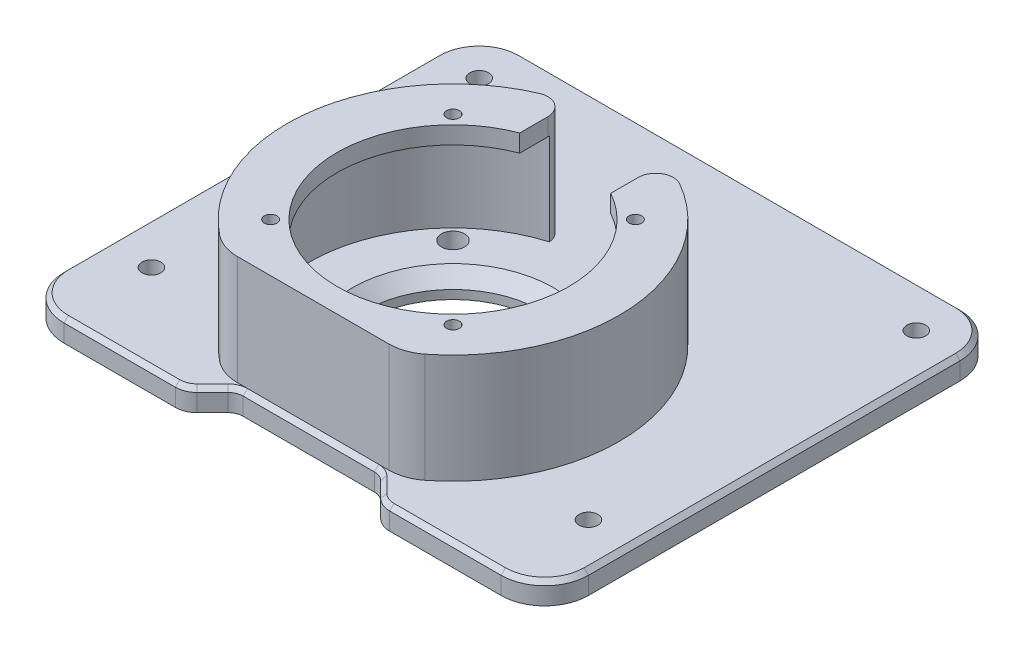
SolidWorks part; units mm, degrees
ref_plane "Front Plane" through (0, 0, 0) normal (0, 0, 1) x (1, 0, 0)
ref_plane "Top Plane" through (0, 0, 0) normal (0, 1, 0) x (1, 0, 0)
ref_plane "Right Plane" through (0, 0, 0) normal (1, 0, 0) x (0, 0, -1)
sketch "Sketch1" plane through (0, 0, 0) normal (0, 1, 0) x (1, 0, 0)
  line L0 (0, 0) -> (0, -28) construction
  line L1 (0, -28) -> (-28, -28) construction
  line L2 (0, -28) -> (28, -28) construction
  line L3 (0, 0) -> (0, 42) construction
  line L4 (0, 42) -> (20, 42) construction
  line L5 (0, 42) -> (-20, 42) construction
  line L6 (-15, -36.5) -> (15, -36.5) construction
  line L7 (-15, -34.85) -> (15, -34.85)
  line L8 (-15, -38.15) -> (15, -38.15)
  line L9 (0, 0) -> (0, -36.5) construction
  circle A0 centre (0, 0) radius 35 construction
  circle A1 centre (28, -28) radius 1.4
  circle A2 centre (-28, -28) radius 1.4
  circle A3 centre (-20, 42) radius 1.4
  circle A4 centre (20, 42) radius 1.4
  arc A5 (-15, -34.85) -> (-15, -38.15) centre (-15, -36.5) ccw
  arc A6 (15, -38.15) -> (15, -34.85) centre (15, -36.5) ccw
  point P15 (0, -36.5)
  dimension "D1" = 70
  dimension "D6" = 2.8
  dimension "D9" = 1.65
  dimension "D2" = 28
  dimension "D3" = 42
  dimension "D4" = 56
  dimension "D5" = 40
  dimension "D7" = 30
  dimension "D8" = 36.5
sketch "Sketch2" plane through (0, 0, 0) normal (0, 1, 0) x (1, 0, 0)
  line L0 (0, 0) -> (0, 66) construction
  line L1 (-60, 66) -> (60, 66)
  line L2 (-60, 66) -> (-60, -39)
  line L4 (60, 66) -> (60, -39)
  line L6 (-60, -39) -> (60, -39)
  dimension "D1" = 120
  dimension "D2" = 105
  dimension "D3" = 66
extrude "Boss-Extrude2" add sketch "Sketch2" along normal blind 5
sketch "Sketch9" plane through (0, 5, 0) normal (0, 1, 0) x (1, 0, 0)
  line L0 (-15, -36.5) -> (15, -36.5) construction
  line L1 (-15, -33) -> (15, -33) construction
  line L2 (-15, -40) -> (15, -40) construction
  line L3 (-17.4749, -34.0251) -> (-23.4497, -40)
  line L4 (-23.4497, -40) -> (23.4497, -40)
  line L5 (23.4497, -40) -> (17.4749, -34.0251)
  line L6 (-15, -33) -> (15, -33)
  arc A0 (-15, -33) -> (-15, -40) centre (-15, -36.5) ccw construction
  arc A1 (15, -40) -> (15, -33) centre (15, -36.5) ccw construction
  arc A2 (-17.4749, -34.0251) -> (-15, -33) centre (-15, -36.5) cw
  arc A3 (15, -33) -> (17.4749, -34.0251) centre (15, -36.5) cw
  point P2 (0, -36.5)
  dimension "D1" = 3.5
  dimension "D2" = 45
extrude "Cut-Extrude7" cut sketch "Sketch9" against normal through all
fillet "Fillet5" radius 10 4 edges at (-60, 2.5, -66) (60, 2.5, -66) (60, 2.5, 39) (-60, 2.5, 39)
sketch "Sketch10" plane through (0, 0, 0) normal (0, 1, 0) x (1, 0, 0)
  circle A0 centre (0, 0) radius 20
  dimension "D1" = 40
extrude "Cut-Extrude9" cut sketch "Sketch10" along normal through all
chamfer "Chamfer3" distance 3 angle 45 1 edges at (0, 5, 20)
fillet "Fillet6" radius 5 2 edges at (-22.4497, 2.5, 39) (22.4497, 2.5, 39)
chamfer "Chamfer4" distance 1 angle 45 16 edges at (-19.2301, 5, 35.7803) (-16.3394, 5, 33.2664) (-22.6074, 5, 38.6194) (0, 5, 33) (-37.2604, 5, 39) (16.3394, 5, 33.2664) (-57.0711, 5, 36.0711) (19.2301, 5, 35.7803) (-60, 5, -13.5) (22.6074, 5, 38.6194) (-57.0711, 5, -63.0711) (37.2604, 5, 39) (0, 5, -66) (57.0711, 5, 36.0711) (57.0711, 5, -63.0711) (60, 5, -13.5)
sketch "Sketch11" plane through (0, 5, 0) normal (0, 1, 0) x (1, 0, 0)
  line L0 (0, 0) -> (0, 42) construction
  line L1 (50, -19) -> (-50, -19) construction
  line L2 (50, -19) -> (50, 56) construction
  line L3 (50, 56) -> (-50, 56) construction
  line L4 (-50, -19) -> (-50, 56) construction
  line L5 (50, -19) -> (-50, 56) construction
  line L6 (50, 56) -> (-50, -19) construction
  circle A0 centre (-50, 56) radius 2.15
  circle A1 centre (50, 56) radius 2.15
  circle A2 centre (-50, -19) radius 2.15
  circle A3 centre (50, -19) radius 2.15
  point P0 (0, 18.5)
  dimension "D4" = 4.3
  dimension "D1" = 100
  dimension "D2" = 56
  dimension "D3" = 75
extrude "Cut-Extrude10" cut sketch "Sketch11" against normal through all
sketch "Sketch13" plane through (0, 0, 0) normal (0, -1, 0) x (1, 0, 0)
  circle A0 centre (-28, 28) radius 3.25
  circle A1 centre (28, 28) radius 3.25
  circle A2 centre (-20, -42) radius 3.25
  circle A3 centre (20, -42) radius 3.25
  dimension "D1" = 6.5
extrude "Cut-Extrude12" [suppressed] cut sketch "Sketch13" against normal blind 2.5
sketch "Sketch27" plane through (0, 5, 0) normal (0, -1, 0) x (1, 0, 0)
  line L0 (-15, 32) -> (-20.4939, 32)
  line L1 (-20.4939, 32) -> (20.4939, 32)
  line L2 (-17.7973, 27.7895) -> (17.7973, 27.7895)
  line L5 (12.8538, -23.2305) -> (12.8538, -35.76)
  line L10 (-9.5142, -24.7863) -> (-9.5142, -36.7897)
  line L11 (-18.182, 33.318) -> (-21.6924, 36.8284)
  line L12 (15, 32) -> (-15, 32)
  line L13 (21.6924, 36.8284) -> (18.182, 33.318)
  line L14 (50, 38) -> (24.5208, 38)
  line L15 (59, -56) -> (59, 29)
  line L16 (-50, -65) -> (50, -65)
  line L17 (-59, 29) -> (-59, -56)
  line L18 (-24.5208, 38) -> (-50, 38)
  line L20 (15, 32) -> (-15, 32)
  arc A0 (12.8538, -35.76) -> (20.4939, 32) centre (0, 0) ccw
  arc A1 (-20.4939, 32) -> (-9.5142, -36.7897) centre (0, 0) ccw
  arc A2 (12.8538, -35.76) -> (20.4939, 32) centre (0, 0) ccw
  arc A5 (-17.7973, 27.7895) -> (-9.5142, -31.5987) centre (0, 0) ccw
  arc A6 (-17.7973, 27.7895) -> (-9.5142, -31.5987) centre (0, 0) ccw
  arc A7 (12.8538, -23.2305) -> (-9.5142, -24.7863) centre (0, 0) ccw
  circle A8 centre (-20.8597, -20.8597) radius 1.45
  circle A9 centre (20.8597, -20.8597) radius 1.45
  circle A10 centre (20.8597, 20.8597) radius 1.45
  circle A11 centre (-20.8597, 20.8597) radius 1.45
  arc A12 (-20.4939, 32) -> (-9.5142, -36.7897) centre (0, 0) ccw
  arc A13 (-20.4939, 32) -> (20.4939, 32) centre (0, 0) ccw construction
  arc A14 (12.8538, -30.3937) -> (17.7973, 27.7895) centre (0, 0) ccw
  arc A15 (-17.7973, 27.7895) -> (17.7973, 27.7895) centre (0, 0) ccw construction
  arc A16 (-17.7973, 27.7895) -> (-8.6842, -31.8368) centre (0, 0) ccw construction
  arc A17 (-20.4939, 32) -> (-10, -36.6606) centre (0, 0) ccw construction
  arc A20 (-21.6924, 36.8284) -> (-24.5208, 38) centre (-24.5208, 34) ccw
  arc A21 (-18.182, 33.318) -> (-15, 32) centre (-15, 36.5) ccw
  arc A22 (15, 32) -> (18.182, 33.318) centre (15, 36.5) ccw
  arc A23 (24.5208, 38) -> (21.6924, 36.8284) centre (24.5208, 34) ccw
  arc A24 (59, 29) -> (50, 38) centre (50, 29) ccw
  arc A25 (50, -65) -> (59, -56) centre (50, -56) ccw
  arc A26 (-59, -56) -> (-50, -65) centre (-50, -56) ccw
  arc A27 (-50, 38) -> (-59, 29) centre (-50, 29) ccw
  point P3 (0, 0)
  point P43 (0, 0)
  point P48 (-12.3083, -23.0016)
  point P49 (0, 0)
  point P53 (-9.5142, -24.7863)
  line M39 (-15, 32) -> (15, 32)
  dimension "D3" = 2.9
  dimension "D4" = 2.9
  dimension "D5" = 2.9
  dimension "D6" = 2.9
  dimension "D1" = 0
  dimension "D2" = 5
extrude "Boss-Extrude3" add sketch "Sketch27" against normal blind 25 contours L5 A14 L2 A5 L10 A1 L0 L1 A0 M39 region at (0, 5, 30.9749)
extrude "Boss-Extrude4" add sketch "Sketch27<3>" along normal blind 4 from surface contours A14 L5 A7 L10 A5 L2 A10 A8 A9 A11 region at (-31.8043, 5, -4.4359) starting at face at (0.4717, 30, -3.1351)
sketch "Sketch27<3>" plane through (0, 5, 0) normal (0, -1, 0) x (1, 0, 0) same geometry as "Sketch27"
sketch "Sketch28" plane through (0, 0, 0) normal (0, -1, 0) x (1, 0, 0)
  circle A0 centre (-20.8597, 20.8597) radius 2.625
  circle A1 centre (20.8597, 20.8597) radius 2.625
  circle A2 centre (20.8597, -20.8597) radius 2.625
  circle A3 centre (-20.8597, -20.8597) radius 2.625
  dimension "D1" = 5.25
  dimension "D2" = 5.25
  dimension "D3" = 5.25
  dimension "D4" = 5.25
extrude "Cut-Extrude13" cut sketch "Sketch28" against normal up to surface (5 mm away) up to face at (50, 5, -53.85)
fillet "Fillet7" radius 10 2 edges at (20.4939, 17.5, 32) (-20.4939, 17.5, 32)
fillet "Fillet8" radius 4 2 edges at (-9.5142, 17.5, -36.7897) (12.8538, 17.5, -35.76)
